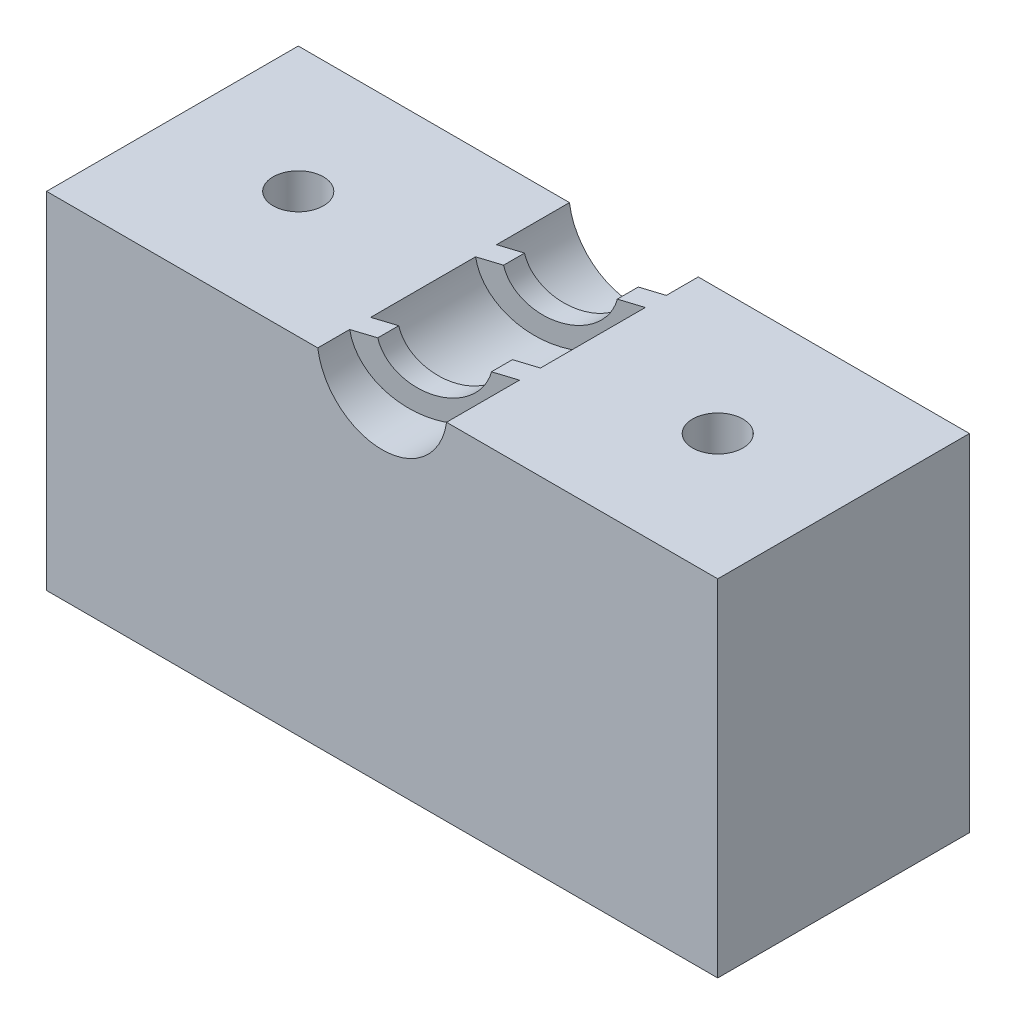
SolidWorks part; units mm, degrees
ref_plane "前视基准面" through (0, 0, 0) normal (0, 0, 1) x (1, 0, 0)
ref_plane "上视基准面" through (0, 0, 0) normal (0, 1, 0) x (1, 0, 0)
ref_plane "右视基准面" through (0, 0, 0) normal (1, 0, 0) x (0, 0, -1)
other "Configuration Table"
sketch "草图1" plane through (0, 0, 0) normal (0, 0, 1) x (1, 0, 0)
  line L1 (-8, -8) -> (8, -8)
  line L2 (-8, -8) -> (-8, 8)
  line L3 (-8, 8) -> (8, 8)
  line L4 (8, -8) -> (8, 8)
  line L5 (-8, -8) -> (8, 8) construction
  line L6 (-8, 8) -> (8, -8) construction
  circle A0 centre (0, 0) radius 1.55
  point P0 (0, 0)
  dimension "D3" = 3.1
  dimension "D1" = 16
  dimension "D2" = 16
extrude "凸台-拉伸1" add sketch "草图1" along normal mid plane 6
sketch "草图6" plane through (0, 0, 0) normal (0, 1, 0) x (1, 0, 0)
  line L0 (-1.55, -3) -> (1.55, -3) construction
  line L1 (1.55, 3) -> (-1.55, 3) construction
  line L2 (-1.55, -3) -> (1.55, -3)
  line L3 (1.55, 3) -> (-1.55, 3)
  line L4 (-1.55, 3) -> (-1.55, -3)
  line L5 (1.55, -3) -> (1.55, 3)
  line L6 (-1.55, 0.7565) -> (1.55, 1.7435)
  line L7 (1.55, 1.7435) -> (1.55, 2.2435)
  line L8 (1.55, 2.2435) -> (-1.55, 1.2565)
  line L9 (-1.55, -1.7435) -> (1.55, -0.7565)
  line L10 (-1.55, -2.2435) -> (1.55, -1.2565)
  line L11 (-2.0945, -0.6668) -> (3.135, 0.9981) construction
  line L12 (-3.1004, 0) -> (4.2723, 0) construction
  dimension "D1" = 2.5
  dimension "D2" = 0.5
  dimension "D3" = 0.5
  dimension "D4" = 17.66
extrude "凸台-拉伸2" add sketch "草图6" against normal up to surface (8 mm away) contours L4 L10 L5 L9 | L5 L8 L4 L6 region at (0, 0, 1.5) region at (0, 0, -1.5) up to face at (0, -8, 0)
sketch "草图7" plane through (0, 0, 0) normal (0, 0, 1) x (1, 0, 0)
  line L0 (0, 0) -> (-1.0279, -0.2141)
  line L1 (0, 0) -> (1.0279, -0.2141)
  line L2 (-1.0279, -0.2141) -> (-8, -0.2141)
  line L3 (1.0279, -0.2141) -> (8, -0.2141)
  line L6 (8, -8) -> (8, 8)
  line L7 (-8, -8) -> (8, -8)
  line L8 (-8, 8) -> (-8, -8)
  line L9 (8, 8) -> (-8, 8)
  line L10 (8, -8) -> (8, 8)
  line L11 (-8, -8) -> (8, -8)
  line L12 (-8, 8) -> (-8, -8)
  line L13 (8, 8) -> (-8, 8)
  circle A0 centre (0, 0) radius 1.05
  dimension "D1" = 2.1
  dimension "D2" = 0
  dimension "D3" = 156.47
extrude "切除-拉伸2" cut sketch "草图7" against normal through all both and the other way through all contours A0 L3 L10 L13 L12 L2 | L1 A0 L0 | L0 A0 L1 region at (0, -0.5019, 0) region at (0, 0.3858, 0) region at (0, 3.953, 0)
sketch "草图8" plane through (0, 0, 0) normal (0, 1, 0) x (1, 0, 0)
  line L0 (0, 5.5834) -> (0, -5.0797) construction
  circle A0 centre (-5, 0) radius 0.6
  circle A1 centre (5, 0) radius 0.6
  dimension "D2" = 1.2
  dimension "D3" = 10
extrude "切除-拉伸3" cut sketch "草图8" against normal through all
sketch "草图9" plane through (0, -8, 0) normal (0, -1, 0) x (1, 0, 0)
  line L4 (-8, -3) -> (8, -3)
  line L5 (8, -3) -> (8, 3)
  line L6 (8, 3) -> (-8, 3)
  line L7 (-8, 3) -> (-8, -3)
  line L8 (-8, -3) -> (8, -3)
  line L9 (8, -3) -> (8, 3)
  line L10 (8, 3) -> (-8, 3)
  line L11 (-8, 3) -> (-8, -3)
  circle A0 centre (-5, 0) radius 0.6 construction
  circle A1 centre (5, 0) radius 0.6 construction
  circle A2 centre (-5, 0) radius 0.6
  circle A3 centre (5, 0) radius 0.6
  dimension "D1" = 0
extrude "凸台-拉伸3" add sketch "草图9" along normal offset from surface (0.455 mm away) 0.5
equation "\"x\"=0.8094"
